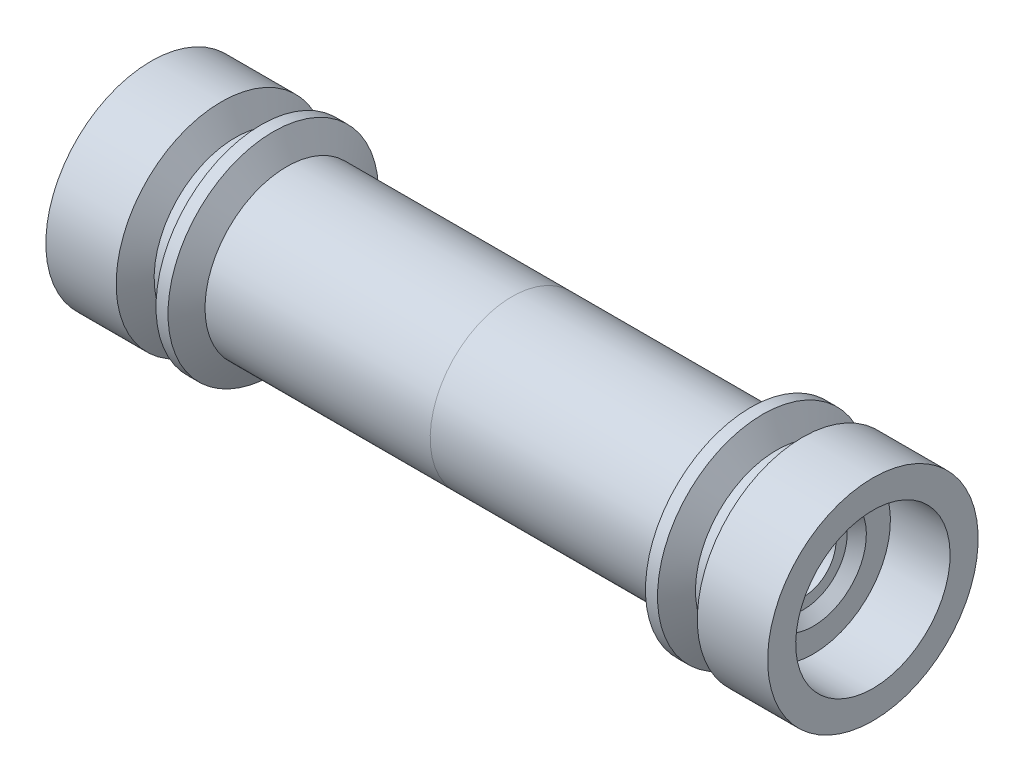
SolidWorks part; units mm, degrees
ref_plane "Front Plane" through (0, 0, 0) normal (0, 0, 1) x (1, 0, 0)
ref_plane "Top Plane" through (0, 0, 0) normal (0, 1, 0) x (1, 0, 0)
ref_plane "Right Plane" through (0, 0, 0) normal (1, 0, 0) x (0, 0, -1)
sketch "Sketch2" plane through (0, 0, 0) normal (0, 0, 1) x (1, 0, 0)
  line L0 (0, 0) -> (0, 28.4375) construction
  line L1 (-19.05, 4.075) -> (-15.9, 4.075) construction
  line L2 (-19.05, 4.075) -> (-19.05, -4.075) construction
  line L3 (-19.05, -4.075) -> (-15.9, -4.075) construction
  line L4 (-15.9, 4.075) -> (-15.9, -4.075) construction
  line L5 (-19.05, 4.075) -> (-15.9, -4.075) construction
  line L6 (-19.05, -4.075) -> (-15.9, 4.075) construction
  line L7 (15.9, 4.5) -> (47.6832, 4.5) construction
  line L8 (15.9, 4.5) -> (15.9, -4.5) construction
  line L9 (15.9, -4.5) -> (47.6832, -4.5) construction
  line L10 (47.6832, 4.5) -> (47.6832, -4.5) construction
  line L11 (15.9, 4.5) -> (47.6832, -4.5) construction
  line L12 (15.9, -4.5) -> (47.6832, 4.5) construction
  line L13 (-19.05, 0) -> (47.6832, 0) construction
  line L14 (-19.05, 5.5562) -> (-15.3382, 5.5562)
  line L21 (-11.8869, 4.318) -> (0, 4.318)
  line L22 (-19.05, 5.5562) -> (-19.05, 4.075)
  line L23 (-19.05, 4.075) -> (-15.9, 4.075)
  line L24 (-15.9, 4.075) -> (-15.9, 0)
  line L25 (-15.9, 0) -> (0, 0)
  line L26 (0, 0) -> (0, 4.318)
  line L27 (-33.5594, -5.5562) -> (-33.5594, 5.5562) construction
  line L28 (-15.3382, 5.5562) -> (-14.605, 4.2862)
  line L29 (-14.605, 4.2862) -> (-13.97, 4.2862)
  line L30 (-19.05, 5.5562) -> (19.05, 5.5562) construction
  line L31 (0, 1.6) -> (-12.5, 1.6)
  line L32 (-12.5, 1.6) -> (-14.1, 0)
  line L33 (-12.5, 1.6) -> (-12.5, -1.6) construction
  line L34 (-12.5, 1.6) -> (12.5, 1.6) construction
  line L35 (-15.9, 1.7145) -> (-9.225, 1.7145)
  line L36 (-9.225, 1.7145) -> (-9.225, 0)
  line L37 (-15.9, 2.805) -> (-15.392, 2.297)
  line L38 (-9.225, 1.7145) -> (-22.225, 1.7145) construction
  line L39 (-9.225, 1.7145) -> (-9.225, -1.7145) construction
  line L40 (-9.225, -1.7145) -> (-22.225, -1.7145) construction
  line L41 (-22.225, 1.7145) -> (-22.225, -1.7145) construction
  line L42 (-15.392, 2.297) -> (-15.392, 0)
  line L46 (-13.97, 4.2862) -> (-13.2368, 5.5562)
  line L47 (-13.2368, 5.5562) -> (-12.6018, 5.5562)
  line L48 (-12.6018, 5.5562) -> (-11.8869, 4.318)
  line L49 (-14.2875, 4.2862) -> (-14.2875, 6.3987) construction
  line L50 (-14.2875, 6.3987) -> (14.2875, 6.3987) construction
  point P0 (-17.475, 0)
  point P5 (31.7916, 0)
  point P27 (-33.5594, 0)
  point P29 (-12.5, 0)
  point P33 (0, 6.3987)
  point P36 (0, 1.6)
  point P48 (-9.225, 0)
  point P51 (0, 5.5562)
  dimension "D3" = 4.318
  dimension "D4" = 11.1125
  dimension "D5" = 8.15
  dimension "D6" = 60
  dimension "D7" = 0.635
  dimension "D8" = 60
  dimension "D9" = 28.575
  dimension "D10" = 1.27
  dimension "D11" = 38.1
  dimension "D12" = 0.635
  dimension "D13" = 45
  dimension "D14" = 25
  dimension "D15" = 3.2
  dimension "D16" = 3.429
  dimension "D17" = 3.175
  dimension "D18" = 1.27
  dimension "D19" = 0.508
  dimension "D20" = 45
  dimension "D21" = 13
  dimension "D22" = 3.15
revolve "Revolve1" add sketch "Sketch2" angle 360 about L13 region at (-9.0476, 3.2674, 0)
mirror "Mirror1" about plane through (0, 0, 0) normal (1, 0, 0) of bodies 101
chamfer "Chamfer1" distance 0.508 angle 45 1 edges at (-19.05, -4.075, 0)
